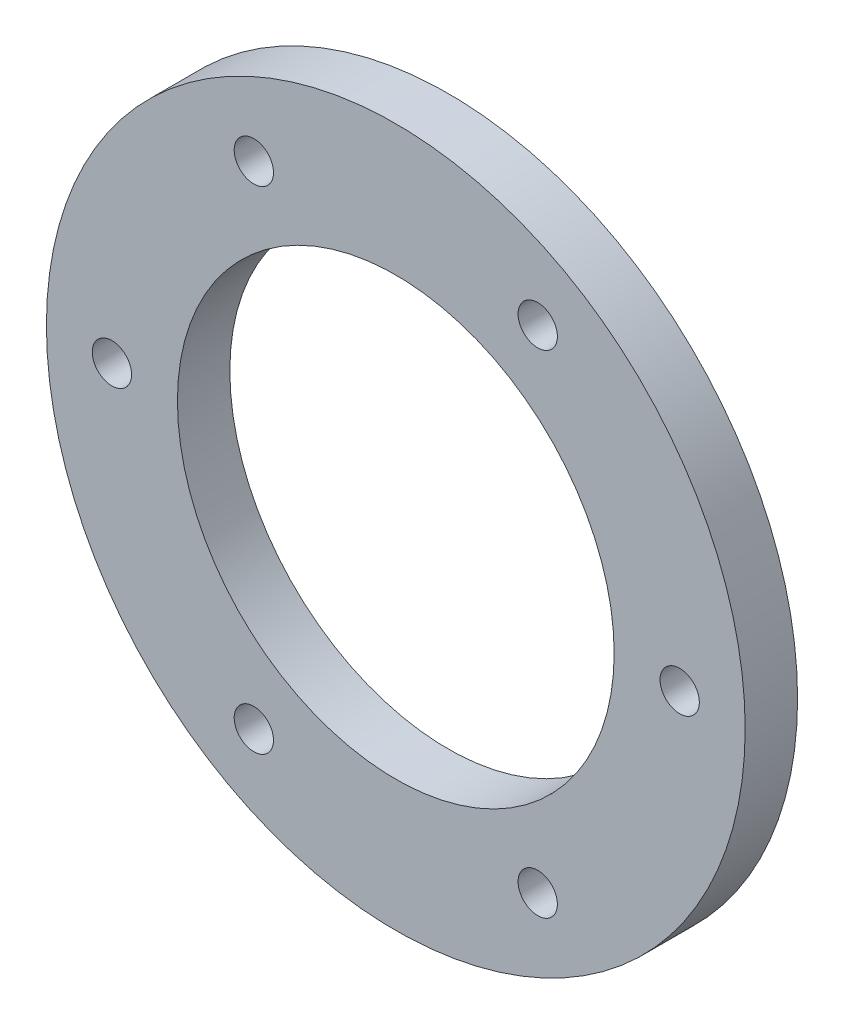
SolidWorks part; units mm, degrees
material "AISI 316 Stainless Steel Sheet (SS)"
ref_plane "Front Plane" through (0, 0, 0) normal (0, 0, 1) x (1, 0, 0)
ref_plane "Top Plane" through (0, 0, 0) normal (0, 1, 0) x (1, 0, 0)
ref_plane "Right Plane" through (0, 0, 0) normal (1, 0, 0) x (0, 0, -1)
sketch "Sketch1" plane through (0, 0, 0) normal (0, 0, 1) x (1, 0, 0)
  circle A0 centre (0, 0) radius 40
  circle A1 centre (0, 0) radius 25
  dimension "D1" = 80
  dimension "D2" = 50
extrude "Boss-Extrude1" add sketch "Sketch1" along normal blind 6
sketch "Sketch2" plane through (0, 0, 0) normal (0, 0, 1) x (1, 0, 0)
  line L0 (0, 0) -> (0, 38.7905) construction
  line L1 (0, 38.7905) -> (0, 0) construction
  line L2 (0, 0) -> (-35.432, 0) construction
  line L3 (-35.432, 0) -> (37.9508, 0) construction
  line L4 (37.9508, 0) -> (0, 0) construction
  line L5 (0, 0) -> (-18.1409, 31.4209) construction
  circle A0 centre (0, 0) radius 32.5 construction
  circle A1 centre (-16.25, 28.1458) radius 2.25
  dimension "D1" = 65
  dimension "D2" = 30
extrude "Cut-Extrude1" cut sketch "Sketch2" along normal through all
pattern_circular "CirPattern1" count 6 over 360 about axis through (0, 0, 6) along (0, 0, 1) of "Cut-Extrude1"
